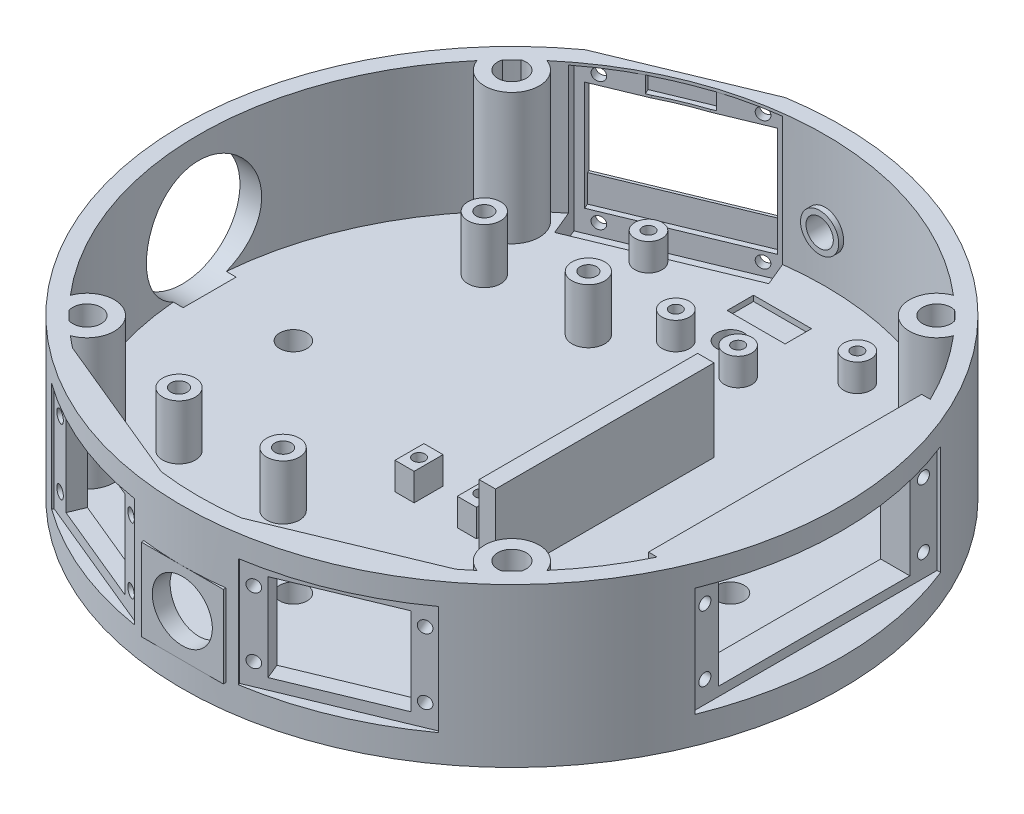
SolidWorks part; units mm, degrees
ref_plane "Front Plane" through (0, 0, 0) normal (0, 0, 1) x (1, 0, 0)
ref_plane "Top Plane" through (0, 0, 0) normal (0, 1, 0) x (1, 0, 0)
ref_plane "Right Plane" through (0, 0, 0) normal (1, 0, 0) x (0, 0, -1)
sketch "Sketch1" plane through (0, 0, 0) normal (0, 1, 0) x (1, 0, 0)
  circle A0 centre (0, 0) radius 60.325
  dimension "D1" = 120.65
extrude "Boss-Extrude1" add sketch "Sketch1" along normal blind 5
sketch "Sketch2" plane through (0, 5, 0) normal (0, 1, 0) x (1, 0, 0)
  line L9 (-15, -10) -> (15, -10)
  line L10 (-15, -10) -> (-15, 30)
  line L11 (-15, 30) -> (15, 30)
  line L12 (15, -10) -> (15, 30)
  line L13 (-15, -10) -> (15, 30) construction
  line L14 (-15, 30) -> (15, -10) construction
  point P0 (0.3114, 20.4789)
  point P5 (0, 10)
  dimension "D1" = 30
  dimension "D2" = 40
  dimension "D3" = 10
  dimension "D4" = 0
extrude "Boss-Extrude2" [suppressed] add sketch "Sketch2" along normal blind 20
sketch "Sketch3" plane through (0, 5, 0) normal (0, 1, 0) x (1, 0, 0)
  circle A0 centre (0, 0) radius 60.325
  circle A1 centre (0, 0) radius 57.325
  dimension "D1" = 114.65
  dimension "D2" = 3
extrude "Boss-Extrude3" add sketch "Sketch3" along normal blind 24
sketch "Sketch5" plane through (0, 5, 0) normal (0, 1, 0) x (1, 0, 0)
  line L0 (0, 0) -> (-38.8909, 38.8909)
  line L1 (0, 0) -> (38.8909, 38.8909)
  line L2 (0, 0) -> (-38.8909, -38.8909)
  line L3 (0, 0) -> (38.8909, -38.8909)
  circle A0 centre (-38.8909, 38.8909) radius 2.6
  circle A1 centre (-38.8909, 38.8909) radius 5
  circle A2 centre (38.8909, 38.8909) radius 2.6
  circle A3 centre (38.8909, 38.8909) radius 5
  circle A4 centre (-38.8909, -38.8909) radius 2.6
  circle A5 centre (-38.8909, -38.8909) radius 5
  circle A6 centre (38.8909, -38.8909) radius 2.6
  circle A7 centre (38.8909, -38.8909) radius 5
  circle A8 centre (0, 0) radius 60.325 construction
  circle M19 centre (0, 0) radius 57.325
  dimension "D1" = 5.2
  dimension "D2" = 10
  dimension "D3" = 5.2
  dimension "D4" = 10
  dimension "D5" = 10
  dimension "D6" = 5.2
  dimension "D7" = 5.2
  dimension "D8" = 10
  dimension "D9" = 55
  dimension "D10" = 55
  dimension "D11" = 55
  dimension "D12" = 55
ref_plane "Plane1" through (0, 0, 60.325) normal (0, 0, 1) x (1, 0, 0)
sketch "Sketch6" plane through (0, 0, 60.325) normal (0, 0, 1) x (1, 0, 0)
  line L1 (-7.5, 19.5) -> (7.5, 19.5)
  line L2 (-7.5, 19.5) -> (-7.5, 4.5)
  line L3 (-7.5, 4.5) -> (7.5, 4.5)
  line L4 (7.5, 19.5) -> (7.5, 4.5)
  line L5 (-7.5, 19.5) -> (7.5, 4.5) construction
  line L6 (-7.5, 4.5) -> (7.5, 19.5) construction
  point P0 (0, 12)
  dimension "D1" = 12
  dimension "D2" = 15
  dimension "D3" = 15
extrude "Boss-Extrude13" add sketch "Sketch6" against normal blind 2
sketch "Sketch7" plane through (0, 0, 60.325) normal (0, 0, 1) x (1, 0, 0)
  circle A0 centre (0, 12.3134) radius 5.5
  dimension "D1" = 11
extrude "Cut-Extrude1" cut sketch "Sketch7" against normal blind 5
sketch "Sketch8" [suppressed] plane through (0, 0, 10) normal (0, 0, 1) x (1, 0, 0)
  line L0 (-15, 5) -> (15, 5) construction
  line L1 (-12.0184, 27.5) -> (12.0184, 27.5)
  line L2 (-12.0184, 27.5) -> (-12.0184, 7.5)
  line L3 (-12.0184, 7.5) -> (12.0184, 7.5)
  line L4 (12.0184, 27.5) -> (12.0184, 7.5)
  line L5 (-12.0184, 27.5) -> (12.0184, 7.5) construction
  line L6 (-12.0184, 7.5) -> (12.0184, 27.5) construction
  point P0 (0, 17.5)
  dimension "D1" = 12.5
  dimension "D2" = 20
extrude "Cut-Extrude2" [suppressed] cut sketch "Sketch8" against normal blind 50
sketch "Sketch11" [suppressed] plane through (-15, 0, 0) normal (-1, 0, 0) x (0, 0, 1)
  line L0 (-30, 5) -> (10, 5) construction
  line L1 (-30, 25) -> (-30, 5) construction
  circle A0 centre (-15, 15) radius 2
  circle A1 centre (4, 15) radius 2
  dimension "D2" = 4
  dimension "D3" = 4
  dimension "D1" = 19
  dimension "D4" = 10
  dimension "D5" = 15
extrude "Cut-Extrude5" [suppressed] cut sketch "Sketch11" against normal blind 20
sketch "Sketch12" [suppressed] plane through (15, 0, 0) normal (1, 0, 0) x (0, 0, -1)
  line L0 (-10, 25) -> (-10, 5) construction
  line L1 (-10, 5) -> (30, 5) construction
  circle A0 centre (3, 15) radius 2
  circle A1 centre (26, 15) radius 2
  dimension "D3" = 4
  dimension "D4" = 4
  dimension "D1" = 23
  dimension "D2" = 13
  dimension "D5" = 10
extrude "Cut-Extrude6" [suppressed] cut sketch "Sketch12" against normal blind 20
ref_plane "Plane2" through (0, 0, -60.325) normal (0, 0, -1) x (-1, 0, 0)
ref_plane "Plane3" through (-60.325, 0, 0) normal (-1, 0, 0) x (0, 0, 1)
sketch "Sketch15" plane through (-60.325, 0, 0) normal (-1, 0, 0) x (0, 0, 1)
  circle A1 centre (0, 14.0795) radius 12.5
  dimension "D1" = 25
extrude "Boss-Extrude15" add sketch "Sketch15" against normal blind 3
sketch "Sketch16" plane through (-60.325, 0, 0) normal (-1, 0, 0) x (0, 0, 1)
  circle A0 centre (0, 14.3674) radius 10.55
  dimension "D1" = 21.1
extrude "Cut-Extrude9" cut sketch "Sketch16" against normal blind 5
sketch "Sketch17" plane through (0, 5, 0) normal (0, 1, 0) x (1, 0, 0)
  circle A0 centre (0, 40) radius 2.5
  circle A1 centre (40, 0) radius 2.5
  circle A2 centre (0, -40) radius 2.5
  circle A3 centre (-40, 0) radius 2.5
  dimension "D5" = 5
  dimension "D6" = 5
  dimension "D7" = 5
  dimension "D8" = 5
  dimension "D1" = 40
  dimension "D2" = 40
  dimension "D3" = 40
  dimension "D4" = 40
extrude "Cut-Extrude10" cut sketch "Sketch17" against normal blind 5
ref_plane "Plane4" through (60.325, 0, 0) normal (1, 0, 0) x (0, 0, -1)
sketch "Sketch20" plane through (0, 5, 0) normal (0, 1, 0) x (1, 0, 0)
  line L1 (-5.1053, 49.3333) -> (5.5119, 49.3333)
  line L2 (-5.1053, 49.3333) -> (-5.1053, 44.4903)
  line L3 (-5.1053, 44.4903) -> (5.5119, 44.4903)
  line L4 (5.5119, 49.3333) -> (5.5119, 44.4903)
  line L5 (-5.1053, 49.3333) -> (5.5119, 44.4903) construction
  line L6 (-5.1053, 44.4903) -> (5.5119, 49.3333) construction
  point P0 (0.2033, 46.9118)
extrude "Cut-Extrude13" cut sketch "Sketch20" against normal blind 1
ref_plane "Plane6" through (50, 0, 0) normal (1, 0, 0) x (0, 0, -1)
sketch "Sketch26" plane through (50, 0, 0) normal (1, 0, 0) x (0, 0, -1)
  line L1 (-25, 5) -> (25, 5)
  line L2 (-25, 5) -> (-25, 29)
  line L3 (-25, 29) -> (25, 29)
  line L4 (25, 5) -> (25, 29)
  line L5 (-25, 5) -> (25, 29) construction
  line L6 (-25, 29) -> (25, 5) construction
  point P0 (0, 17)
  dimension "D1" = 0
  dimension "D2" = 17
  dimension "D3" = 24
  dimension "D4" = 50
extrude "Boss-Extrude46" add sketch "Sketch26" along normal blind 10
sketch "Sketch27" plane through (60.325, 0, 0) normal (1, 0, 0) x (0, 0, -1)
  line L1 (-22.5, 5) -> (22.5, 5)
  line L2 (-22.5, 5) -> (-22.5, 25)
  line L3 (-22.5, 25) -> (22.5, 25)
  line L4 (22.5, 5) -> (22.5, 25)
  line L5 (-22.5, 5) -> (22.5, 25) construction
  line L6 (-22.5, 25) -> (22.5, 5) construction
  point P0 (0, 15)
  dimension "D1" = 45
  dimension "D2" = 20
  dimension "D3" = 0
  dimension "D4" = 15
extrude "Cut-Extrude15" cut sketch "Sketch27" against normal blind 5
sketch "Sketch28" plane through (60.325, 0, 0) normal (1, 0, 0) x (0, 0, -1)
  line L1 (-17.5, 23.3481) -> (17.5, 23.3481)
  line L2 (-17.5, 23.3481) -> (-17.5, 6.6519)
  line L3 (-17.5, 6.6519) -> (17.5, 6.6519)
  line L4 (17.5, 23.3481) -> (17.5, 6.6519)
  line L5 (-17.5, 23.3481) -> (17.5, 6.6519) construction
  line L6 (-17.5, 6.6519) -> (17.5, 23.3481) construction
  point P0 (0, 15)
  dimension "D1" = 35
  dimension "D2" = 15
  dimension "D3" = 0
sketch "Sketch29" plane through (55.325, 0, 0) normal (1, 0, 0) x (0, 0, -1)
  circle A0 centre (-20, 21) radius 1.1
  circle A1 centre (-20, 9) radius 1.1
  circle A2 centre (20, 21) radius 1.1
  circle A3 centre (20, 9.1519) radius 1.1
  dimension "D1" = 2.2
  dimension "D2" = 2.2
  dimension "D3" = 2.2
  dimension "D4" = 2.2
  dimension "D5" = 40
  dimension "D6" = 12
  dimension "D7" = 9
extrude "Cut-Extrude17" cut sketch "Sketch29" against normal blind 10
extrude "Cut-Extrude18" cut sketch "Sketch28" against normal blind 20
sketch "Sketch30" plane through (0, 29, 0) normal (0, 1, 0) x (1, 0, 0)
  line L0 (51.7831, 30.9453) -> (68.4097, 30.9453)
  line L1 (50.8846, -32.4016) -> (67.7321, -32.4016)
  arc A0 (50.8846, -32.4016) -> (51.7831, 30.9453) centre (0, 0) ccw
  arc A1 (67.7321, -32.4016) -> (68.4097, 30.9453) centre (0, 0) ccw
  dimension "D1" = 120.65
extrude "Boss-Extrude47" add sketch "Sketch5" along normal blind 24 contours L0 A1 A0 M19 | A1 L0 A0 M19 | A5 L2 A4 M19 | L2 A5 A4 M19 | A7 L3 A6 M19 | L3 A7 A6 M19 | L1 A3 A2 M19 | A3 L1 A2 M19 region at (-39.8437, 5, -35.9068) region at (-35.9068, 5, -39.8437) region at (35.9068, 5, -39.8437) region at (39.8437, 5, -35.9068) region at (-35.9068, 5, 39.8437) region at (-39.8437, 5, 35.9068) region at (39.8437, 5, 35.9068) region at (35.9068, 5, 39.8437)
extrude "Cut-Extrude19" cut sketch "Sketch30" against normal blind 30
sketch "Sketch31" plane through (0, 5, 0) normal (0, 1, 0) x (1, 0, 0)
  circle A0 centre (-33.05, 28) radius 3
  circle A1 centre (-14, 28) radius 3
  circle A2 centre (-14, -27.88) radius 3
  circle A3 centre (-33.05, -27.88) radius 3
  dimension "D9" = 6
  dimension "D10" = 6
  dimension "D11" = 6
  dimension "D12" = 6
  dimension "D2" = 55.88
  dimension "D3" = 14
  dimension "D4" = 14
  dimension "D5" = 19.05
  dimension "D6" = 28
  dimension "D7" = 55.88
  dimension "D8" = 0
  dimension "D13" = 19.05
extrude "Boss-Extrude48" add sketch "Sketch31" along normal blind 10
sketch "Sketch32" plane through (0, 15, 0) normal (0, 1, 0) x (1, 0, 0)
  circle A0 centre (-14, -27.88) radius 1.5
  circle A1 centre (-33.05, -27.88) radius 1.5
  circle A2 centre (-33.05, 28) radius 1.5
  circle A3 centre (-14, 28) radius 1.5
  dimension "D1" = 3
  dimension "D2" = 3
  dimension "D3" = 3
  dimension "D4" = 3
extrude "Cut-Extrude20" cut sketch "Sketch32" against normal blind 5
sketch "Sketch33" plane through (0, 5, 0) normal (0, 1, 0) x (1, 0, 0)
  line L9 (-6.75, -14.6471) -> (-3.25, -14.6471)
  line L10 (-6.75, -14.6471) -> (-6.75, -9.3529)
  line L11 (-6.75, -9.3529) -> (-3.25, -9.3529)
  line L12 (-3.25, -14.6471) -> (-3.25, -9.3529)
  line L13 (-6.75, -14.6471) -> (-3.25, -9.3529) construction
  line L14 (-6.75, -9.3529) -> (-3.25, -14.6471) construction
  line L15 (4.65, -14.6471) -> (8.15, -14.6471)
  line L16 (4.65, -14.6471) -> (4.65, -9.3529)
  line L17 (4.65, -9.3529) -> (8.15, -9.3529)
  line L18 (8.15, -14.6471) -> (8.15, -9.3529)
  line L19 (4.65, -14.6471) -> (8.15, -9.3529) construction
  line L20 (4.65, -9.3529) -> (8.15, -14.6471) construction
  circle A0 centre (-5, 35) radius 2.5
  circle A1 centre (6.4, 35.005) radius 2.5
  point P12 (-5, -12)
  point P17 (6.4, -12)
  dimension "D1" = 5
  dimension "D2" = 5
  dimension "D3" = 11.4
  dimension "D4" = 11.4
  dimension "D5" = 47
  dimension "D6" = 12
  dimension "D7" = 5
  dimension "D8" = 3.5
  dimension "D9" = 3.5
  dimension "D10" = 5
extrude "Boss-Extrude49" add sketch "Sketch33" along normal blind 5
sketch "Sketch34" plane through (0, 10, 0) normal (0, 1, 0) x (1, 0, 0)
  circle A1 centre (6.4, 35.005) radius 1.1
  circle A2 centre (6.4, -12) radius 1.1
  circle A3 centre (-5, -12) radius 1.1
  circle A4 centre (-5, 35) radius 1.1
  dimension "D1" = 2.2
  dimension "D2" = 2.2
  dimension "D3" = 2.2
  dimension "D4" = 2.2
  dimension "D5" = 12
  dimension "D6" = 12
extrude "Cut-Extrude21" cut sketch "Sketch34" against normal blind 5
sketch "Sketch35" plane through (0, 5, 0) normal (0, 1, 0) x (1, 0, 0)
  line L1 (14, 20) -> (17, 20)
  line L2 (14, 20) -> (14, -20)
  line L3 (14, -20) -> (17, -20)
  line L4 (17, 20) -> (17, -20)
  dimension "D1" = 17
  dimension "D2" = 3
  dimension "D3" = 40
  dimension "D4" = 20
extrude "Boss-Extrude50" add sketch "Sketch35" along normal blind 15
ref_axis "Axis1" through (0, 28.35, 0) along (0, -1, 0)
ref_plane "Plane8" through (-23.0854, 0, 55.733) normal (-0.3827, 0, 0.9239) x (0, -1, 0)
ref_plane "Plane9" through (0, 0, 0) normal (0.9239, 0, 0.3827) x (0, -1, 0)
ref_plane "Plane10" through (23.0854, 0, 55.733) normal (0.3827, 0, 0.9239) x (0, -1, 0)
ref_plane "Plane11" through (21.172, 0, 51.1136) normal (0.3827, 0, 0.9239) x (0, -1, 0)
sketch "Sketch39" plane through (21.172, 0, 51.1136) normal (0.3827, 0, 0.9239) x (0, -1, 0)
  line L1 (-29, 15.0144) -> (-5, 15.0144)
  line L2 (-29, 15.0144) -> (-29, -14.9856)
  line L3 (-29, -14.9856) -> (-5, -14.9856)
  line L4 (-5, 15.0144) -> (-5, -14.9856)
  dimension "D1" = 24
  dimension "D2" = 5
  dimension "D3" = 30
extrude "Boss-Extrude51" add sketch "Sketch39" along normal blind 2
sketch "Sketch37" plane through (23.0854, 0, 55.733) normal (0.3827, 0, 0.9239) x (0, -1, 0)
  line L1 (-25, 14) -> (-5, 14)
  line L2 (-25, 14) -> (-25, -14)
  line L3 (-25, -14) -> (-5, -14)
  line L4 (-5, 14) -> (-5, -14)
  dimension "D1" = 20
  dimension "D2" = 5
  dimension "D3" = 28
  dimension "D4" = 14
extrude "Cut-Extrude25" cut sketch "Sketch37" against normal blind 2
sketch "Sketch40" plane through (23.0854, 0, 55.733) normal (0.3827, 0, 0.9239) x (0, -1, 0)
  line L1 (-23, 10) -> (-7, 10)
  line L2 (-23, 10) -> (-23, -10)
  line L3 (-23, -10) -> (-7, -10)
  line L4 (-7, 10) -> (-7, -10)
  dimension "D1" = 16
  dimension "D2" = 7
  dimension "D3" = 10
  dimension "D4" = 20
extrude "Cut-Extrude26" cut sketch "Sketch40" against normal blind 12
sketch "Sketch41" plane through (23.0854, 0, 55.733) normal (0.3827, 0, 0.9239) x (0, -1, 0)
  circle A0 centre (-21, 12) radius 1.1
  circle A1 centre (-9, 12) radius 1.1
  circle A2 centre (-9, -12) radius 1.1
  circle A3 centre (-21, -12) radius 1.1
  dimension "D5" = 2.2
  dimension "D6" = 2.2
  dimension "D7" = 2.2
  dimension "D8" = 2.2
  dimension "D1" = 12
  dimension "D2" = 9
  dimension "D3" = 12
  dimension "D4" = 9
  dimension "D9" = 24
  dimension "D10" = 24
  dimension "D11" = 12
  dimension "D12" = 12
extrude "Cut-Extrude27" cut sketch "Sketch41" against normal blind 12
mirror "Mirror2" about plane through (0, 0, 0) normal (1, 0, 0) of "Boss-Extrude51", "Cut-Extrude25", "Cut-Extrude26", "Cut-Extrude27"
ref_plane "Plane12" through (-20.9232, 0, -50.5131) normal (0.3827, 0, 0.9239) x (0, -1, 0)
sketch "Sketch43" plane through (-20.9232, 0, -50.5131) normal (0.3827, 0, 0.9239) x (0, -1, 0)
  line L1 (-28.5, 15) -> (-1, 15)
  line L2 (-28.5, 15) -> (-28.5, -15)
  line L3 (-28.5, -15) -> (-1, -15)
  line L4 (-1, 15) -> (-1, -15)
  dimension "D1" = 30
  dimension "D2" = 27.5
  dimension "D3" = 1
  dimension "D4" = 15
extrude "Cut-Extrude28" cut sketch "Sketch43" against normal blind 2.5 and the other way blind 4
sketch "Sketch44" plane through (0, 5, 0) normal (0, 1, 0) x (1, 0, 0)
  circle A0 centre (-20, 45) radius 2.5
  circle A1 centre (45, -30) radius 2.5
  circle A2 centre (18.2295, 45) radius 2.5
  circle A3 centre (18.2295, -32.0272) radius 2.5
  dimension "D3" = 5
  dimension "D4" = 5
  dimension "D5" = 5
  dimension "D8" = 5
  dimension "D1" = 20
  dimension "D2" = 45
  dimension "D6" = 45
  dimension "D7" = 30
extrude "Boss-Extrude52" add sketch "Sketch44" along normal blind 5
sketch "Sketch45" plane through (0, 10, 0) normal (0, 1, 0) x (1, 0, 0)
  circle A0 centre (-20, 45) radius 1.1
  circle A1 centre (18.2295, 45) radius 1.1
  circle A2 centre (18.2295, -32.0272) radius 1.1
  circle A3 centre (45, -30) radius 1.1
  dimension "D1" = 2.2
  dimension "D2" = 2.2
  dimension "D3" = 2.2
  dimension "D4" = 2.2
extrude "Cut-Extrude29" cut sketch "Sketch45" against normal blind 5
sketch "Sketch46" plane through (-21.8799, 0, -52.8228) normal (0.3827, 0, 0.9239) x (0.9239, 0, -0.3827)
  line L1 (-13.5, 25) -> (13.5, 25)
  line L2 (-13.5, 25) -> (-13.5, 10)
  line L3 (-13.5, 10) -> (13.5, 10)
  line L4 (13.5, 25) -> (13.5, 10)
  dimension "D1" = 27
  dimension "D2" = 15
  dimension "D3" = 10
  dimension "D4" = 13.5
extrude "Cut-Extrude30" cut sketch "Sketch46" against normal blind 5
sketch "Sketch47" plane through (-21.8799, 0, -52.8228) normal (0.3827, 0, 0.9239) x (0.9239, 0, -0.3827)
  circle A0 centre (11.5, 26.75) radius 1.1
  circle A1 centre (-11.5, 26.75) radius 1.1
  circle A2 centre (-11.5, 3.25) radius 1.1
  circle A3 centre (11.5, 3.25) radius 1.1
  dimension "D4" = 2.2
  dimension "D5" = 2.2
  dimension "D6" = 2.2
  dimension "D7" = 2.2
  dimension "D1" = 23
  dimension "D2" = 23.5
  dimension "D3" = 23
  dimension "D8" = 3.25
  dimension "D9" = 11.5
extrude "Cut-Extrude31" cut sketch "Sketch47" against normal blind 3
ref_plane "Plane13" through (-22.454, 0, -54.2086) normal (0.3827, 0, 0.9239) x (0, -1, 0)
sketch "Sketch48" plane through (-22.454, 0, -54.2086) normal (0.3827, 0, 0.9239) x (0, -1, 0)
  line L1 (-35, 15) -> (5, 15)
  line L2 (-35, 15) -> (-35, -15)
  line L3 (-35, -15) -> (5, -15)
  line L4 (5, 15) -> (5, -15)
  dimension "D1" = 30
  dimension "D2" = 15
  dimension "D3" = 5
  dimension "D4" = 40
extrude "Cut-Extrude32" cut sketch "Sketch48" against normal blind 5
sketch "Sketch49" plane through (-21.8799, 0, -52.8228) normal (0.3827, 0, 0.9239) x (0.9239, 0, -0.3827)
  line L1 (-5, 28.45) -> (5, 28.45)
  line L2 (-5, 28.45) -> (-5, 25.45)
  line L3 (-5, 25.45) -> (5, 25.45)
  line L4 (5, 28.45) -> (5, 25.45)
  line L5 (-13.5, 10) -> (13.5, 10)
  line L6 (-13.5, 10) -> (-13.5, 5)
  line L7 (-13.5, 5) -> (13.5, 5)
  line L8 (13.5, 10) -> (13.5, 5)
  dimension "D1" = 10
  dimension "D2" = 3
  dimension "D3" = 5
  dimension "D4" = 27
  dimension "D5" = 13.5
  dimension "D6" = 5
  dimension "D7" = 5
extrude "Cut-Extrude33" cut sketch "Sketch49" against normal blind 1
sketch "Sketch52" plane through (0, 0, -60.325) normal (0, 0, -1) x (-1, 0, 0)
  line L0 (0, 28.35) -> (0, -1.35) construction
  circle A0 centre (0, 14) radius 3.5
  dimension "D1" = 7
  dimension "D2" = 14
extrude "Boss-Extrude54" add sketch "Sketch52" against normal blind 4
sketch "Sketch53" plane through (0, 0, -60.325) normal (0, 0, -1) x (-1, 0, 0)
  line L0 (0, 28.35) -> (0, -1.35) construction
  circle A0 centre (0, 14) radius 2.5
  dimension "D1" = 5
  dimension "D2" = 14
extrude "Cut-Extrude34" cut sketch "Sketch53" against normal blind 4
